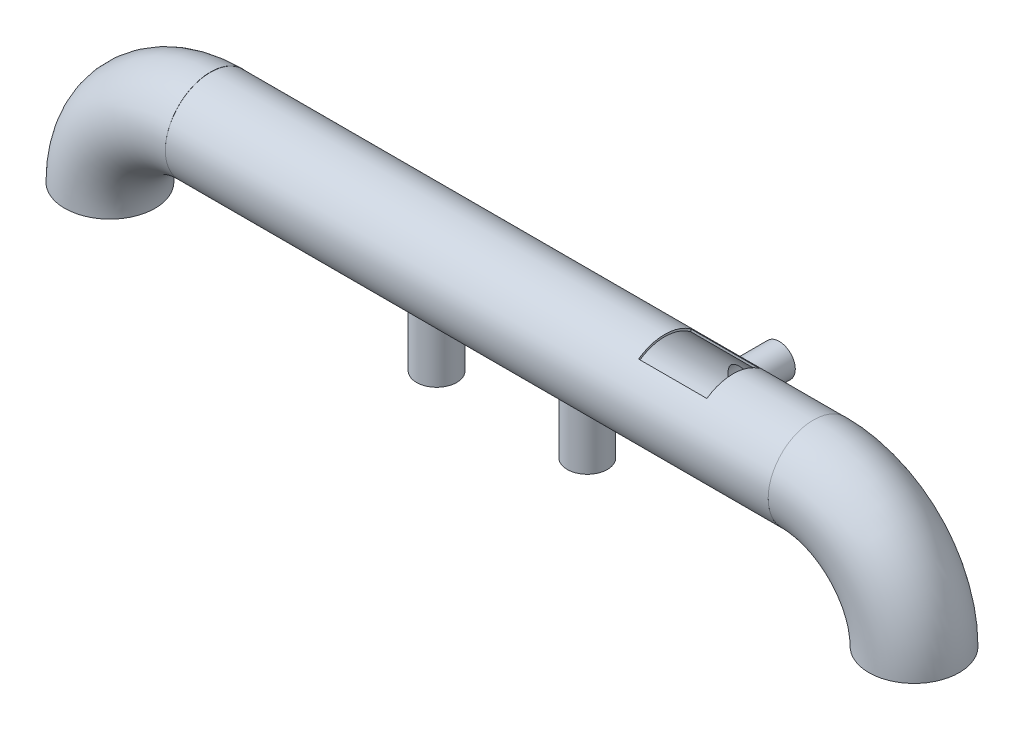
SolidWorks part; units mm, degrees
ref_plane "Alzado" through (0, 0, 0) normal (0, 0, 1) x (1, 0, 0)
ref_plane "Planta" through (0, 0, 0) normal (0, 1, 0) x (1, 0, 0)
ref_plane "Vista lateral" through (0, 0, 0) normal (1, 0, 0) x (0, 0, -1)
sketch "Croquis1" plane through (0, 0, 0) normal (0, 1, 0) x (1, 0, 0)
  line L0 (-55, 0) -> (55, 0) construction
  line L1 (0, -55) -> (0, 55) construction
  circle A0 centre (-37.5, 0) radius 10
  circle A1 centre (37.5, 0) radius 10
  point P8 (20.0178, 15.7753)
  dimension "D1" = 20
  dimension "D2" = 20
  dimension "D3" = 75
  dimension "D4" = 37.5
extrude "Saliente-Extruir1" add sketch "Croquis1" along normal blind 40
sketch "Croquis2" plane through (0, 0, 0) normal (1, 0, 0) x (0, 0, -1)
  line L0 (0, 22) -> (0, -22) construction
  line L1 (11, 0) -> (-11, 0) construction
  circle A0 centre (0, 50) radius 22.5
  dimension "D1" = 45
  dimension "D2" = 0
  dimension "D3" = 50
extrude "Saliente-Extruir2" add sketch "Croquis2" along normal blind 150 and the other way blind 150
sketch "Croquis6" plane through (150, 0, -150) normal (-1, 0, 0) x (0, 0, 1)
  circle A0 centre (150, 50.1024) radius 22.5
  circle A1 centre (150, 50.1024) radius 21.5
  point P3 (0, 0)
  dimension "D1" = 43
  dimension "D2" = 45
ref_axis "Eje1" through (150, 0, 25.625) along (0, 0, -1)
revolve "Revolución1" add sketch "Croquis6" angle 90 about axis through (150, 0, 25.625) along (0, 0, -1)
mirror "Simetría1" about plane through (0, 0, 0) normal (1, 0, 0) of "Revolución1"
sketch "Croquis7" plane through (0, 0, 0) normal (0, 1, 0) x (1, 0, 0)
  line L0 (-39.875, 0) -> (39.875, 0) construction
  line L1 (110, -13) -> (76, -13)
  line L2 (110, -13) -> (110, 13)
  line L3 (110, 13) -> (76, 13)
  line L4 (76, -13) -> (76, 13)
  line L5 (110, -13) -> (76, 13) construction
  line L6 (110, 13) -> (76, -13) construction
  line L7 (150, -25.625) -> (150, 43.125) construction
  point P0 (93, 0)
  dimension "D1" = 26
  dimension "D2" = 34
  dimension "D3" = 40
extrude "Cortar-Extruir2" cut sketch "Croquis7" along normal blind 20 from offset 60
sketch "Croquis8" plane through (0, 0, 0) normal (0, 0, 1) x (1, 0, 0)
  line L2 (76, 72.5) -> (-150, 72.5) construction
  line L3 (150, 27.5) -> (150, 50.0512) construction
  circle A0 centre (93, 50) radius 8
  point P5 (0, 0)
  point P7 (69.2477, 72.5)
  dimension "D1" = 16
  dimension "D2" = 22.5
  dimension "D3" = 57
extrude "Saliente-Extruir3" add sketch "Croquis8" against normal blind 40
sketch "Croquis9" plane through (0, 0, -40) normal (0, 0, -1) x (-1, 0, 0)
  circle A0 centre (-93, 50) radius 7
  dimension "D1" = 14
extrude "Cortar-Extruir3" cut sketch "Croquis9" along normal blind 25 from surface starting at face at (93, 64.1822, -13)
sketch "Croquis4" plane through (150, 0, 0) normal (1, 0, 0) x (0, 0, -1)
  circle A0 centre (0, 50) radius 21.5
  dimension "D1" = 43
extrude "Cortar-Extruir1" cut sketch "Croquis4" against normal blind 296
